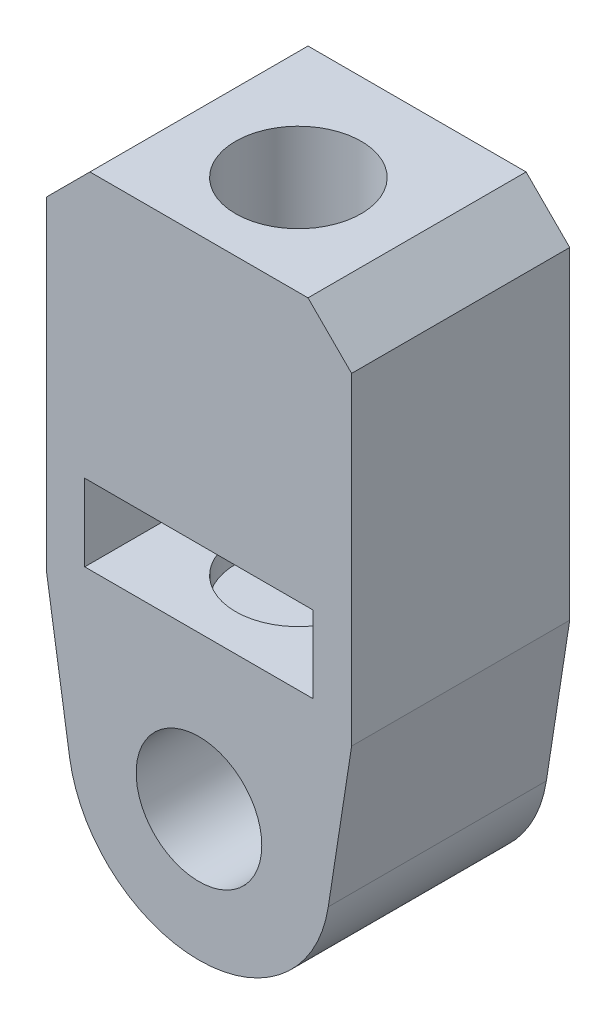
SolidWorks part; units mm, degrees
ref_plane "Front Plane" through (0, 0, 0) normal (0, 0, 1) x (1, 0, 0)
ref_plane "Top Plane" through (0, 0, 0) normal (0, 1, 0) x (1, 0, 0)
ref_plane "Right Plane" through (0, 0, 0) normal (1, 0, 0) x (0, 0, -1)
sketch "Sketch1" plane through (0, 0, 0) normal (0, 0, 1) x (1, 0, 0)
  line L0 (-5.5562, 4.7625) -> (-5.5562, 18.0975)
  line L1 (-5.5562, 18.0975) -> (5.5562, 18.0975)
  line L2 (5.5562, 18.0975) -> (5.5562, 4.7625)
  line L3 (-5.5562, 4.7625) -> (-4.7065, -0.7284)
  line L4 (4.7065, -0.7284) -> (5.5562, 4.7625)
  circle A1 centre (0, 0) radius 2.286
  arc A2 (-4.7065, -0.7284) -> (4.7065, -0.7284) centre (0, 0) ccw
  point P10 (0, 18.0975)
  dimension "D1" = 9.525
  dimension "D2" = 4.572
  dimension "D3" = 13.335
  dimension "D4" = 11.1125
  dimension "D5" = 4.7625
extrude "Boss-Extrude1" add sketch "Sketch1" along normal up to surface (7.9375 mm away)
sketch "Sketch2" plane through (0, 18.0975, 0) normal (0, 1, 0) x (1, 0, 0)
  circle A1 centre (0, -4.3188) radius 2.286
  circle A2 centre (0, -4.3188) radius 1.7525 construction
  dimension "D1" = 4.572
extrude "Cut-Extrude1" cut sketch "Sketch2" against normal offset from surface (13.335 mm away) 4.7625 up to plane "Top Plane"
sketch "Sketch3" plane through (0, 4.7625, 0) normal (0, 1, 0) x (1, 0, 0)
  line L11 (5.5562, -7.9375) -> (-5.5562, -7.9375) construction
  line L12 (-1.9064, -1.0168) -> (-4.1565, -4.9141)
  line L16 (4.1565, -4.9141) -> (1.9064, -1.0168)
  line L17 (1.9064, -1.0168) -> (-1.9064, -1.0168)
  line L18 (-4.1565, -4.9141) -> (-4.1565, -7.9375)
  line L19 (-4.1565, -7.9375) -> (4.1565, -7.9375)
  line L20 (4.1565, -7.9375) -> (4.1565, -4.9141)
  line L22 (-1.9064, -7.6208) -> (0, -7.6208) [skipped]
  line L23 (-3.8128, -4.3188) -> (-2.8596, -5.9698) [skipped]
  line L24 (2.1818, -7.1438) -> (2.8596, -5.9698) [skipped]
  circle A0 centre (0, -4.3188) radius 3.302 construction
  dimension "D1" = 6.604
extrude "Cut-Extrude2" cut sketch "Sketch3" along normal blind 2.794 from offset 0.7937
chamfer "Chamfer1" distance 1.5875 angle 45 2 edges at (5.5562, 18.0975, 3.9688) (-5.5562, 18.0975, 3.9688)
